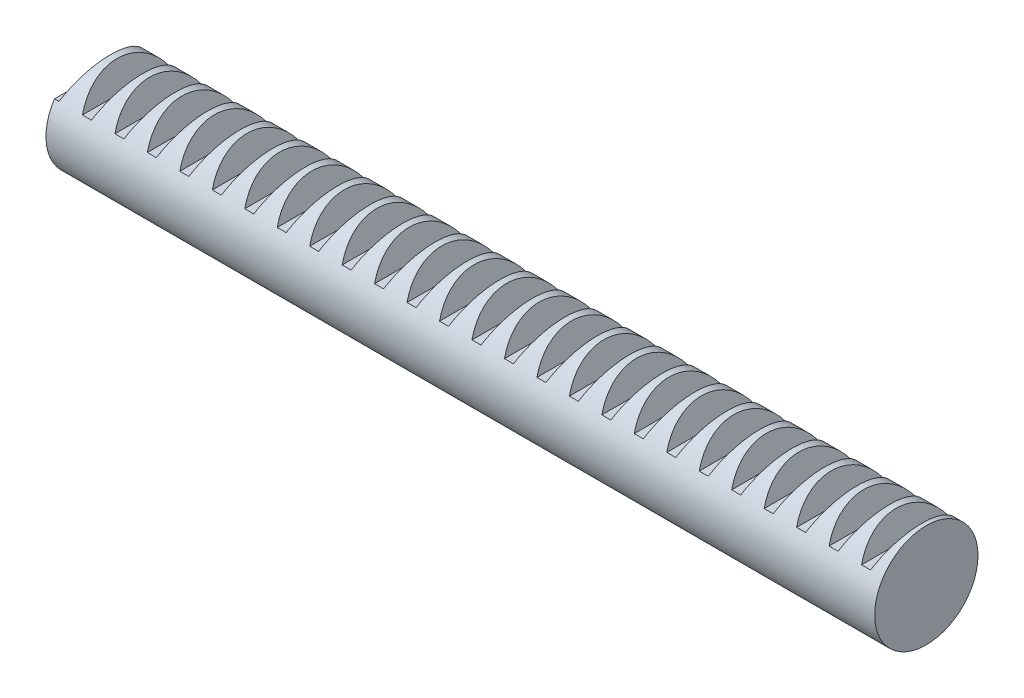
SolidWorks part; units mm, degrees
extrude "Blank" add sketch "BlankSke" against normal blind 25
sketch "BlankSke" plane through (0, 0, 0) normal (0, 0, 1) x (1, 0, 0)
  line L1 (0, 0) -> (500, 0)
  line L2 (0, 0) -> (0, 27.5)
  line L3 (0, 27.5) -> (500, 27.5)
  line L4 (500, 0) -> (500, 27.5)
  dimension "Length" = 500
  dimension "Blank_height" = 27.5
ref_plane "Plane1" through (0, 0, 0) normal (0, 0, 1) x (1, 0, 0)
ref_plane "Plane2" through (0, 0, 0) normal (0, 1, 0) x (1, 0, 0)
ref_plane "Plane3" through (0, 0, 0) normal (1, 0, 0) x (0, 0, -1)
sketch "HoldingSke" plane through (0, 0, 0) normal (0, 1, 0) x (1, 0, 0)
  line L0 (0, 0) -> (0.0557, 0.3961)
  line L1 (-15, 0) -> (100, 0) construction
  line L2 (0, 0) -> (-2.1039, 2.3779)
  line L3 (0, 0) -> (-11.863, 4.5341)
  line L4 (0, 0) -> (3.6497, 7.8269)
  line L5 (0, 0) -> (-23.7986, -8.8762)
  line L6 (0, 0) -> (-10.5278, -7.1032)
  line L9 (-71.009, 38.7566) -> (398.8373, 209.7667)
  line L10 (-76.2, 4.8779) -> (-51.2, 4.8779)
  line L11 (0, 0) -> (-25, 0)
  line L12 (-76.2, 101.6) -> (-76.113, 101.6)
  line L13 (24.9733, 27.94) -> (52.9518, 28.4284)
  line L14 (24.9733, 27.94) -> (24.9743, 27.94)
  line L15 (24.9733, 27.94) -> (100.4006, 29.5858)
  circle A0 centre (0, 0) radius 19.05
  circle A1 centre (0, 0) radius 12.5
  circle A2 centre (0, 0) radius 12.7
  dimension "MPH" = 25
  dimension "Diameter" = 38.1
  dimension "Num_teeth" = 65
  dimension "Pitch" = 0.4
  dimension "Show_teeth" = 998
  dimension "Thickness" = 12.7
  dimension "Ap" = 20
  dimension "Pitch_height" = 25
  dimension "Width" = 25
  dimension "Backlash" = 0.087
  dimension "Addendum_fac" = 1
  dimension "Dedendum_fac" = 1.25
  dimension "Clearance_fac" = 0.25
  dimension "Dedendum_add" = 0.001
  dimension "Length" = 500
  dimension "Module" = 2.5
sketch "TooCutSkeIll" plane through (0, 0, 0) normal (0, 0, 1) x (1, 0, 0)
  line L0 (-3.1105, 27.4342) -> (-1.237, 22.2869)
  line L1 (-0.6488, 21.875) -> (0.6488, 21.875)
  line L2 (1.237, 22.2869) -> (3.1105, 27.4342)
  line L3 (500, 27.5) -> (0, 27.5) construction
  line L4 (0, 0) -> (0, 64.897) construction
  line L5 (-13.208, 25) -> (12.954, 25) construction
  line L6 (0, 0) -> (500, 0) construction
  line L7 (2.2245, 25) -> (2.2245, 48.7463) construction
  line L8 (-2.2245, 25) -> (-2.2245, 48.7463) construction
  line L9 (3.2044, 27.5) -> (3.2044, 27.5254)
  line L10 (-3.2044, 27.5) -> (-3.2044, 27.5254)
  line L11 (-3.2044, 27.5254) -> (3.2044, 27.5254)
  arc A0 (0.6488, 21.875) -> (1.237, 22.2869) centre (0.6488, 22.501) ccw
  arc A1 (-1.237, 22.2869) -> (-0.6488, 21.875) centre (-0.6488, 22.501) ccw
  arc A2 (3.2044, 27.5) -> (3.1105, 27.4342) centre (3.2044, 27.4) ccw
  arc A3 (-3.1105, 27.4342) -> (-3.2044, 27.5) centre (-3.2044, 27.4) ccw
  dimension "Pitch_height" = 25
  dimension "Addendum_plus" = 2.5254
  dimension "Pressure_angle" = 20
  dimension "Gap_width" = 4.449
  dimension "Dedendum" = 3.125
sketch "TooCutSkeSim" plane through (0, 0, 0) normal (0, 0, 1) x (1, 0, 0)
  line L0 (1.0871, 21.875) -> (-1.0871, 21.875)
  line L1 (3.1437, 27.5254) -> (1.0871, 21.875)
  line L2 (0, 17.4625) -> (0, 53.467) construction
  line L3 (3.1437, 27.5254) -> (-3.1437, 27.5254)
  line L6 (-3.1437, 27.5254) -> (-1.0871, 21.875)
  line L9 (-2.2245, 25) -> (2.2245, 25) construction
  line L10 (0, 0) -> (500, 0) construction
  line L11 (2.2245, 25) -> (2.2245, 53.467) construction
  line L12 (-2.2245, 25) -> (-2.2245, 53.467) construction
  dimension "Pitch_height" = 25
  dimension "Addendum_plus" = 2.5254
  dimension "Pressure_angle" = 20
  dimension "Gap_width" = 4.449
  dimension "Dedendum" = 3.125
extrude "ToothCutSim" cut sketch "TooCutSkeSim" against normal through all
pattern_linear "TeethCuts" count 65 spacing 7.854 along (1, 0, 0) of "ToothCutSim"
sketch "Sketch1" plane through (0, 0, 0) normal (0, -1, 0) x (1, 0, 0)
  line L1 (0, 0) -> (500, 0)
  line L2 (0, 0) -> (0, -25)
  line L3 (0, -25) -> (500, -25)
  line L4 (500, 0) -> (500, -25)
extrude "Cut-Extrude1" cut sketch "Sketch1" against normal blind 2.5
sketch "Sketch2" plane through (500, 0, 0) normal (1, 0, 0) x (0, 0, -1)
  line L1 (0, 2.5) -> (25, 2.5)
  line L2 (0, 2.5) -> (0, 27.5)
  circle A0 centre (12.5, 15) radius 12.5
  circle A1 centre (12.5, 15) radius 21.615
  line M1 (0, 26.1823) -> (0, 2.5)
  line M2 (0, 2.5) -> (25, 2.5)
  line M3 (25, 2.5) -> (25, 26.1823)
  line M4 (25, 26.1823) -> (0, 26.1823)
extrude "Cut-Extrude2" cut sketch "Sketch2" against normal blind 666.5 contours A1 A0 L1 L2 M4 M3 M2 M1 | A0 M3 M4 | A0 M4 M1 | A0 L2 M2 | A0 L1 M3 region at (500, 5.2921, -2.7921) region at (500, 5.2921, -22.2079) region at (500, 23.5638, -1.9175) region at (500, 23.5638, -23.0825) region at (500, 15, 8.5037)
ref_plane "Plane4" through (0, 0, -12.5) normal (0, 0, 1) x (1, 0, 0)
extrude "Cut-Extrude3" cut sketch "Sketch3" against normal blind 299.5
sketch "Sketch3" plane through (500, 66.0814, 9.3901) normal (1, 0, 0) x (0, 0, 1)
  circle A0 centre (-21.8901, 51.0814) radius 12.55
equation "' \"Module@HoldingSke\" = 6.35"
equation "' \"Num_teeth@HoldingSke\" = 12"
equation "' \"Ap@HoldingSke\" =  20"
equation "' \"Ap@HoldingSke\" = 20"
equation "' \"Width@HoldingSke\" = 0.25 * 25.4"
equation "' \"Show_teeth@HoldingSke\" = 500"
equation "' \"Backlash@HoldingSke\" = 0.009 * 25.4"
equation "' \"Addendum_fac@HoldingSke\" = 1.0"
equation "' \"Dedendum_fac@HoldingSke\" = 1.25"
equation "' \"Dedendum_add@HoldingSke\" = 0.00005 * 25.4"
equation "' \"Clearance_fac@HoldingSke\" = 0.25"
equation "' \"Pitch_height@HoldingSke\" = 1 * 25.4"
equation "' \"Length@HoldingSke\" = 4.71 * 25.4"
equation "\"Pitch@HoldingSke\" = 1 / \"Module@HoldingSke\""
equation "\"MPH@HoldingSke\" = \"Dedendum_fac@HoldingSke\" / \"Pitch@HoldingSke\" + 2 * \"Dedendum_add@HoldingSke\" + 0.002 * 25.4"
equation "\"MPH@HoldingSke\" = ((sgn( \"MPH@HoldingSke\" - \"Pitch_height@HoldingSke\")+1)*( \"MPH@HoldingSke\" - \"Pitch_height@HoldingSke\"))/2 + \"Pitch_height@HoldingSke\""
equation "\"Blank_height@BlankSke\" = \"Pitch_height@HoldingSke\" + \"Addendum_fac@HoldingSke\"  / \"Pitch@HoldingSke\" "
equation "\"Length@BlankSke\" =  \"Length@HoldingSke\""
equation "\"Face_width@Blank\" = \"Width@HoldingSke\""
equation "\"Pressure_angle@TooCutSkeIll\" = \"Ap@HoldingSke\""
equation "\"Addendum_plus@TooCutSkeIll\" =  \"Addendum_fac@HoldingSke\"  / \"Pitch@HoldingSke\" + 0.001 *25.4"
equation "\"Dedendum@TooCutSkeIll\" = \"Dedendum_fac@HoldingSke\"  / \"Pitch@HoldingSke\""
equation "\"Pitch_height@TooCutSkeIll\" =  \"MPH@HoldingSke\""
equation "\"Gap_width@TooCutSkeIll\" = 3.14159265 / 2 / \"Pitch@HoldingSke\" + 6 * \"Backlash@HoldingSke\""
equation "\"Pressure_angle@TooCutSkeSim\" = \"Ap@HoldingSke\""
equation "\"Addendum_plus@TooCutSkeSim\" =  \"Addendum_fac@HoldingSke\"  / \"Pitch@HoldingSke\" + 0.001 * 25.4"
equation "\"Dedendum@TooCutSkeSim\" = \"Dedendum_fac@HoldingSke\"  / \"Pitch@HoldingSke\""
equation "\"Pitch_height@TooCutSkeSim\" =  \"MPH@HoldingSke\""
equation "\"Gap_width@TooCutSkeSim\" = 3.14159265 / 2 / \"Pitch@HoldingSke\" + 6 * \"Backlash@HoldingSke\""
equation "\"Root_fillet@TooCutSkeIll\" = \"Clearance_fac@HoldingSke\" / \"Pitch@HoldingSke\" + \"Dedendum_add@HoldingSke\""
equation "\"Break_rad@TooCutSkeIll\" = 0.02 / \"Pitch@HoldingSke\" * 2"
equation "\"Linear_pitch@TeethCuts\" = 3.14159265 / \"Pitch@HoldingSke\""
equation "\"Num_teeth@HoldingSke\" = int( ( \"Length@HoldingSke\" + 0 ) / (3.14159265 / \"Pitch@HoldingSke\")) + 0.9999  + 1"
equation " \"Num_teeth@TeethCuts\" = int( \"Show_teeth@HoldingSke\" ) + 1"
equation " \"Num_teeth@TeethCuts\" = ((sgn( \"Num_teeth@TeethCuts\" - \"Num_teeth@HoldingSke\" )-1)*( \"Num_teeth@TeethCuts\" - \"Num_teeth@HoldingSke\" ))/-2+ \"Num_teeth@HoldingSke\""
equation " \"Num_teeth@TeethCuts\" = ((sgn( \"Num_teeth@TeethCuts\" - 2.0)+1)*( \"Num_teeth@TeethCuts\" - 2.0))/2 +2.0"
